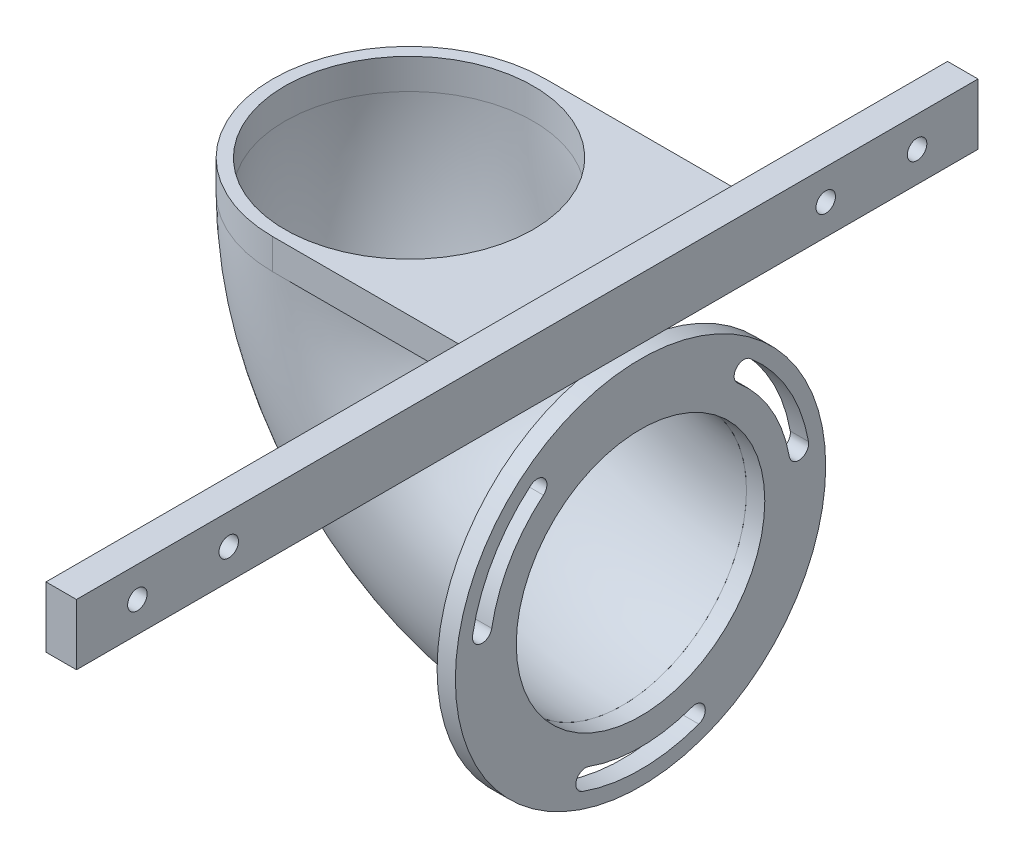
SolidWorks part; units mm, degrees
ref_plane "Front Plane" through (0, 0, 0) normal (0, 0, 1) x (1, 0, 0)
ref_plane "Top Plane" through (0, 0, 0) normal (0, 1, 0) x (1, 0, 0)
ref_plane "Right Plane" through (0, 0, 0) normal (1, 0, 0) x (0, 0, -1)
sketch "Sketch1" plane through (0, 0, 0) normal (1, 0, 0) x (0, 0, -1)
  line L0 (0, 87.5341) -> (0, -84.8074) construction
  line L1 (0, -40) -> (-11.8836, -72.6499) construction
  line L2 (-90.7713, -5) -> (91.3136, -5)
  circle A0 centre (0, -40) radius 20.4
  circle A1 centre (0, -40) radius 22.4
  circle A2 centre (0, -40) radius 30.4
  arc A3 (9.0293, -64.8079) -> (-9.0293, -64.8079) centre (0, -40) cw construction
  arc A4 (-9.5766, -66.3114) -> (9.5766, -66.3114) centre (0, -40) ccw
  arc A5 (-8.4821, -63.3044) -> (8.4821, -63.3044) centre (0, -40) ccw
  arc A6 (-8.4821, -63.3044) -> (-9.5766, -66.3114) centre (-9.0293, -64.8079) ccw
  arc A7 (9.5766, -66.3114) -> (8.4821, -63.3044) centre (9.0293, -64.8079) ccw
  arc A8 (-25.9989, -35.4157) -> (-16.9696, -19.7764) centre (0, -40) cw construction
  arc A9 (-17.9981, -18.5508) -> (-27.5746, -35.1379) centre (0, -40) ccw
  arc A10 (-15.9411, -21.0021) -> (-24.4232, -35.6935) centre (0, -40) ccw
  arc A11 (-15.9411, -21.0021) -> (-17.9981, -18.5508) centre (-16.9696, -19.7764) ccw
  arc A12 (-27.5746, -35.1379) -> (-24.4232, -35.6935) centre (-25.9989, -35.4157) ccw
  arc A13 (16.9696, -19.7764) -> (25.9989, -35.4157) centre (0, -40) cw construction
  arc A14 (27.5746, -35.1379) -> (17.9981, -18.5508) centre (0, -40) ccw
  arc A15 (24.4232, -35.6935) -> (15.9411, -21.0021) centre (0, -40) ccw
  arc A16 (24.4232, -35.6935) -> (27.5746, -35.1379) centre (25.9989, -35.4157) ccw
  arc A17 (17.9981, -18.5508) -> (15.9411, -21.0021) centre (16.9696, -19.7764) ccw
  point P9 (0, -66.4)
  point P20 (-22.8631, -26.8)
  point P27 (22.8631, -26.8)
  dimension "D1" = 40.8
  dimension "D2" = 2
  dimension "D3" = 10
  dimension "D5" = 1.6
  dimension "D6" = 26.4
  dimension "D7" = 40
  dimension "D9" = 35
  dimension "D4" = 20
  dimension "D8" = 3
revolve "Revolve1" add sketch "Sketch1" angle 90 about L2 region at (0, -40, 21.7664)
extrude "Boss-Extrude1" add sketch "Sketch1<194>" along normal blind 3 separate body contours A2 A17 A14 A16 A15 A12 A9 A11 A10 A7 A4 A6 A5 A1 | A1 A0 region at (0, -40, 21.7664) region at (0, -40, 29.5402)
sketch "Sketch1<194>" plane through (0, 0, 0) normal (1, 0, 0) x (0, 0, -1) same geometry as "Sketch1"
sketch "Sketch4" plane through (0, -5, 0) normal (0, 1, 0) x (1, 0, 0)
  line L0 (3, -30.4) -> (3, 30.4) construction
  line L1 (3, -22.4) -> (3, 22.4)
  line L2 (3, -22.4) -> (-35, -22.4)
  line L3 (3, 22.4) -> (-35, 22.4)
  circle A0 centre (-35, 0) radius 22.4 construction
  arc A1 (-35, 22.4) -> (-35, -22.4) centre (-35, 0) ccw
  circle A2 centre (-35, 0) radius 20.4 construction
  circle A3 centre (-35, 0) radius 20.4
  dimension "D1" = 38
extrude "Boss-Extrude3" add sketch "Sketch4" along normal blind 5
sketch "Sketch5" plane through (3, 0, 0) normal (1, 0, 0) x (0, 0, -1)
  line L0 (-156.5441, -2.5) -> (55.1127, -2.5) construction
  line L1 (-22.4, 0) -> (22.4, 0) construction
  line L2 (-22.4, -5) -> (22.4, -5) construction
  line L4 (-92.6, 2.5) -> (55.4, 2.5)
  line L5 (-92.6, 2.5) -> (-92.6, -7.5)
  line L6 (-92.6, -7.5) -> (55.4, -7.5)
  line L7 (55.4, 2.5) -> (55.4, -7.5)
  line L8 (-92.6, 2.5) -> (55.4, -7.5) construction
  line L9 (-92.6, -7.5) -> (55.4, 2.5) construction
  line L10 (22.4, 0) -> (22.4, -5) construction
  circle A0 centre (30.4, -2.5) radius 1.6
  circle A1 centre (45.4, -2.5) radius 1.6
  circle A2 centre (-82.6, -2.5) radius 1.6
  circle A3 centre (-67.6, -2.5) radius 1.6
  point P6 (-18.6, -2.5)
  dimension "D2" = 3.2
  dimension "D4" = 15
  dimension "D5" = 10
  dimension "D3" = 98
  dimension "D6" = 15
  dimension "D1" = 10
  dimension "D7" = 10
  dimension "D8" = 8
extrude "Boss-Extrude4" add sketch "Sketch5" against normal blind 5
